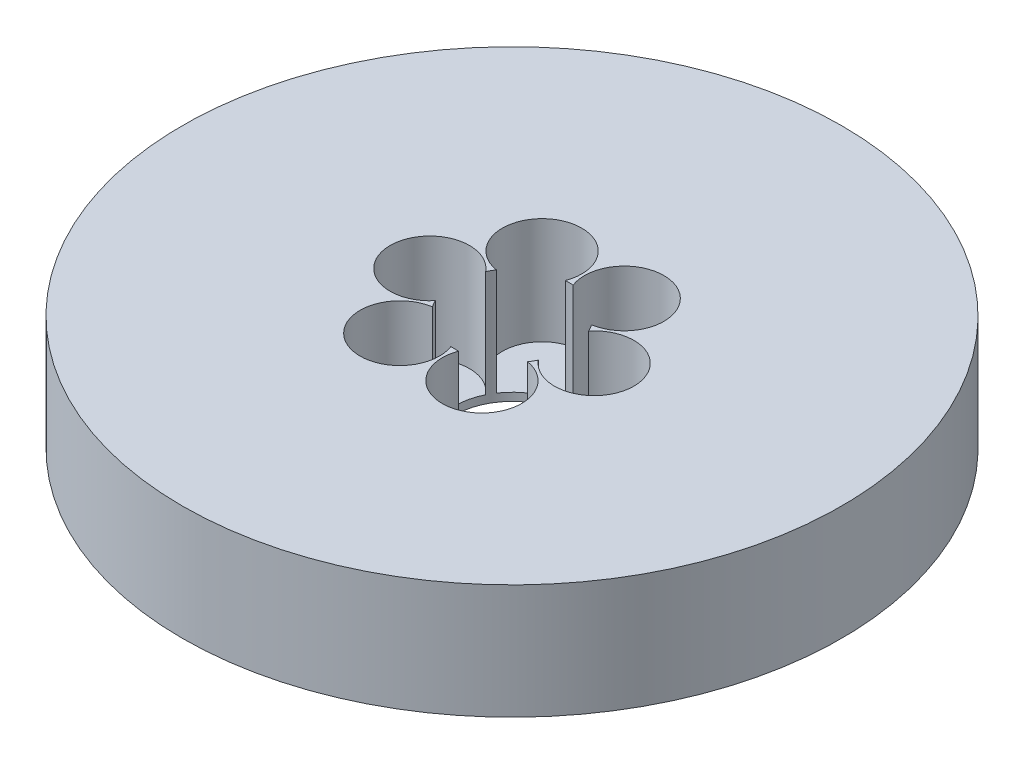
SolidWorks part; units mm, degrees
ref_plane "Front Plane" through (0, 0, 0) normal (0, 0, 1) x (1, 0, 0)
ref_plane "Top Plane" through (0, 0, 0) normal (0, 1, 0) x (1, 0, 0)
ref_plane "Right Plane" through (0, 0, 0) normal (1, 0, 0) x (0, 0, -1)
sketch "Sketch1" plane through (0, 0, 0) normal (0, 1, 0) x (1, 0, 0)
  circle A0 centre (0, 0) radius 57.5
  dimension "FLANGE_OD" = 115
extrude "Boss-Extrude1" add sketch "Sketch1" along normal blind 20
sketch "Sketch2" plane through (0, 0, 0) normal (0, 1, 0) x (1, 0, 0)
  circle A0 centre (0, 0) radius 10
  dimension "BORE_D" = 20
extrude "Cut-Extrude1" cut sketch "Sketch2" along normal through all
sketch "Sketch3" plane through (0, 20, 0) normal (0, 1, 0) x (1, 0, 0)
  circle A0 centre (0, 0) radius 14.3355 construction
  circle A1 centre (-14.3355, 0) radius 6.9281
  dimension "BOLT_D" = 13.8562
  dimension "BOLT_PCD" = 28.6709
extrude "Cut-Extrude2" cut sketch "Sketch3" against normal blind 18.611
pattern_circular "CirPattern1" count 6 over 360 about axis through (0, 0, 0) along (0, 1, 0) of "Cut-Extrude2"
